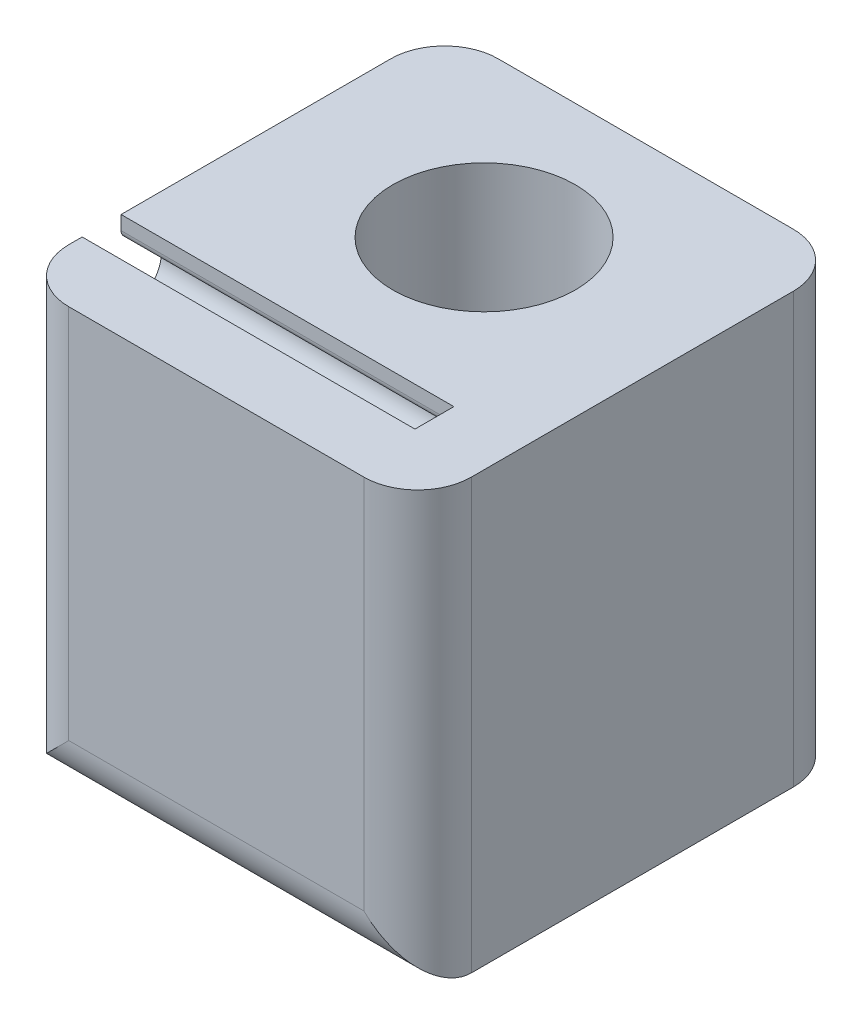
SolidWorks part; units mm, degrees
ref_plane "Front Plane" through (0, 0, 0) normal (0, 0, 1) x (1, 0, 0)
ref_plane "Top Plane" through (0, 0, 0) normal (0, 1, 0) x (1, 0, 0)
ref_plane "Right Plane" through (0, 0, 0) normal (1, 0, 0) x (0, 0, -1)
sketch "Sketch1" plane through (0, 0, 0) normal (1, 0, 0) x (0, 0, -1)
  line L1 (-4, -4) -> (4, -4)
  line L2 (-4, -4) -> (-4, 4)
  line L3 (-4, 4) -> (4, 4)
  line L4 (4, -4) -> (4, 4)
  line L5 (-4, -4) -> (4, 4) construction
  line L6 (-4, 4) -> (4, -4) construction
  point P0 (0, 0)
  dimension "D1" = 8
  dimension "D2" = 8
extrude "Boss-Extrude1" add sketch "Sketch1" along normal blind 7.5
sketch "Sketch2" plane through (0, 0, 0) normal (1, 0, 0) x (0, 0, -1)
  line L0 (-2.025, 4) -> (-2.025, 3.7402)
  line L1 (4, 4) -> (-4, 4) construction
  line L2 (-1.275, 3) -> (-2.025, 3) construction
  line L4 (-2.025, 2) -> (-2.025, 2.2598)
  line L5 (-2.75, 4) -> (-2.75, -4)
  line L6 (-4, -4) -> (4, -4) construction
  line L7 (-2.025, 4) -> (-2.75, 4)
  line L8 (-4, 4) -> (-4, -4) construction
  line L9 (-2.025, 2) -> (-2.025, 1.7402)
  line L10 (-2.025, 0) -> (-2.025, 0.2598)
  line L11 (-1.275, 1) -> (-2.025, 1) construction
  line L12 (-2.025, 0) -> (-2.025, -0.2598)
  line L13 (-2.025, -2) -> (-2.025, -1.7402)
  line L14 (-1.275, -1) -> (-2.025, -1) construction
  line L15 (-2.025, -2) -> (-2.025, -2.2598)
  line L16 (-2.025, -4) -> (-2.025, -3.7402)
  line L17 (-1.275, -3) -> (-2.025, -3) construction
  line L18 (-2.025, -4) -> (-2.75, -4)
  arc A0 (-2.025, 3.7402) -> (-1.8946, 3.5915) centre (-1.875, 3.7402) ccw
  arc A1 (-1.8946, 3.5915) -> (-1.5868, 3.4989) centre (-2.025, 2.6) cw
  arc A2 (-1.5868, 3.4989) -> (-1.5868, 2.5011) centre (-1.83, 3) cw
  arc A3 (-2.025, 2.2598) -> (-1.8946, 2.4085) centre (-1.875, 2.2598) cw
  arc A4 (-1.8946, 2.4085) -> (-1.5868, 2.5011) centre (-2.025, 3.4) ccw
  arc A5 (-2.025, 1.7402) -> (-1.8946, 1.5915) centre (-1.875, 1.7402) ccw
  arc A6 (-1.8946, 1.5915) -> (-1.5868, 1.4989) centre (-2.025, 0.6) cw
  arc A7 (-1.5868, 1.4989) -> (-1.5868, 0.5011) centre (-1.83, 1) cw
  arc A8 (-2.025, 0.2598) -> (-1.8946, 0.4085) centre (-1.875, 0.2598) cw
  arc A9 (-1.8946, 0.4085) -> (-1.5868, 0.5011) centre (-2.025, 1.4) ccw
  arc A10 (-2.025, -0.2598) -> (-1.8946, -0.4085) centre (-1.875, -0.2598) ccw
  arc A11 (-1.8946, -0.4085) -> (-1.5868, -0.5011) centre (-2.025, -1.4) cw
  arc A12 (-1.5868, -0.5011) -> (-1.5868, -1.4989) centre (-1.83, -1) cw
  arc A13 (-2.025, -1.7402) -> (-1.8946, -1.5915) centre (-1.875, -1.7402) cw
  arc A14 (-1.8946, -1.5915) -> (-1.5868, -1.4989) centre (-2.025, -0.6) ccw
  arc A15 (-2.025, -2.2598) -> (-1.8946, -2.4085) centre (-1.875, -2.2598) ccw
  arc A16 (-1.8946, -2.4085) -> (-1.5868, -2.5011) centre (-2.025, -3.4) cw
  arc A17 (-1.5868, -2.5011) -> (-1.5868, -3.4989) centre (-1.83, -3) cw
  arc A18 (-2.025, -3.7402) -> (-1.8946, -3.5915) centre (-1.875, -3.7402) cw
  arc A19 (-1.8946, -3.5915) -> (-1.5868, -3.4989) centre (-2.025, -2.6) ccw
  dimension "D1" = 0.555
  dimension "D2" = 1
  dimension "D3" = 0.15
  dimension "D4" = 0.75
  dimension "D5" = 0.4
  dimension "D6" = 1
  dimension "D7" = 0.725
  dimension "D8" = 1.25
  dimension "D10" = 2
  dimension "D11" = 1.475
  dimension "D9" = 4
extrude "Cut-Extrude1" cut sketch "Sketch2" along normal blind 6.2
hole_wizard "M3 Clearance Hole1" positions "Sketch5" profile "Sketch4" hole size "M3" standard "ANSI Metric" end condition through all
sketch "Sketch5" plane through (0, 4, 0) normal (0, 1, 0) x (1, 0, 0)
  line L0 (0, 4) -> (0, -2.025) construction
  line L1 (7.5, 4) -> (0, 4) construction
  point P0 (3.75, 0.9875)
  point P9 (3.75, 4)
  point P10 (0, 0.9875)
sketch "Sketch4" plane through (3.75, 4, -0.9875) normal (1, 0, 0) x (0, 0, 1)
  line L0 (0, 0) -> (0, 8)
  line L1 (0, 8) -> (1.7, 8)
  line L2 (1.7, 8) -> (1.7, 0)
  line L5 (1.7, 0) -> (0, 0)
  line L11 (0, -6.35) -> (0, 107.95) construction
  dimension "Thru Hole Dia." = 3.4
  dimension "Thru Hole Depth" = 8
fillet "Fillet1" radius 1 5 edges at (3.75, -4, 4) (7.5, 0, 4) (7.5, 0, -4) (0, 0, -4) (0, 0, 4)
